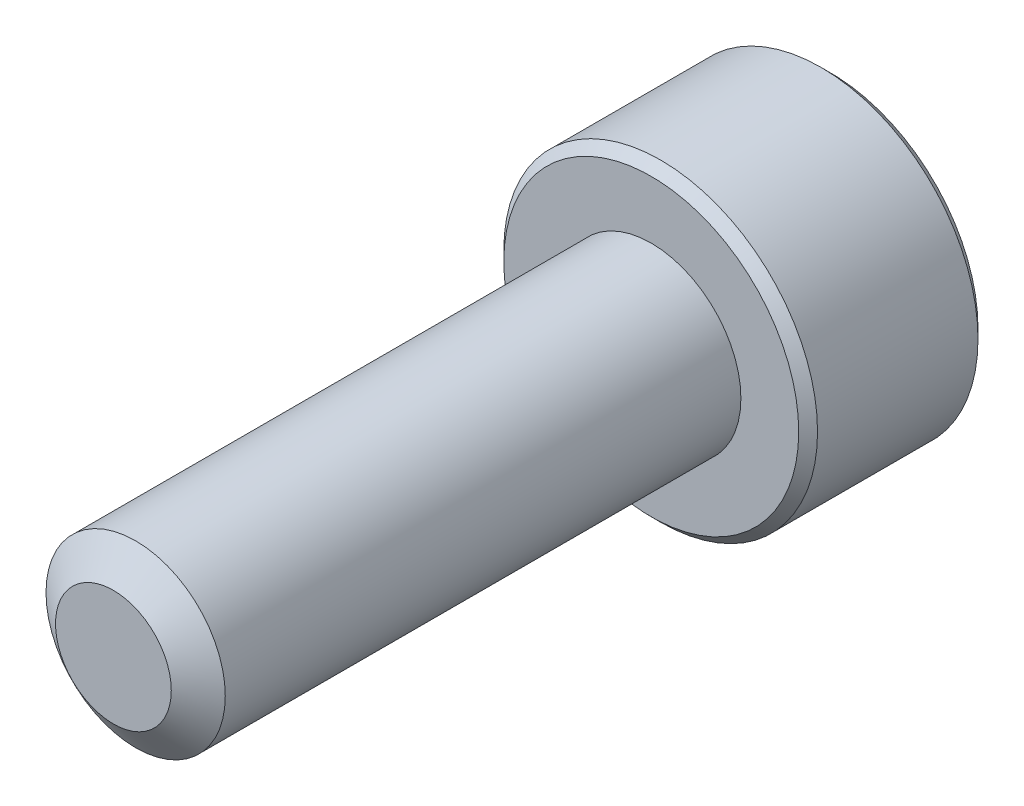
SolidWorks part; units mm, degrees
ref_plane "Front Plane" through (0, 0, 0) normal (0, 0, 1) x (1, 0, 0)
ref_plane "Top Plane" through (0, 0, 0) normal (0, 1, 0) x (1, 0, 0)
ref_plane "Right Plane" through (0, 0, 0) normal (1, 0, 0) x (0, 0, -1)
sketch "Sketch1" plane through (0, 0, 0) normal (0, 0, 1) x (1, 0, 0)
  circle A0 centre (0, 0) radius 2
  dimension "OD" = 4
extrude "Extrude1" add sketch "Sketch1" against normal blind 12
sketch "Sketch2" plane through (0, 0, 0) normal (0, 0, 1) x (1, 0, 0)
  circle A0 centre (0, 0) radius 2 construction
  circle A1 centre (0, 0) radius 2
curve "Helix/Spiral1" pitch 0.7 height 12.7 turns 18.1429 parameters "pitch"=0.7
sketch "Sketch3" plane through (0, 0, 0) normal (1, 0, 0) x (0, 0, -1)
  line L0 (-0.6125, 2) -> (-0.35, 1.5453)
  line L1 (-0.35, 1.5453) -> (-0.2625, 1.5453)
  line L2 (-0.2625, 1.5453) -> (0, 2)
  line L3 (-0.6125, 2) -> (0, 2)
  line L4 (-0.3063, 2) -> (-0.3063, 1.5453) construction
  line L5 (-0.4813, 1.7727) -> (-0.1313, 1.7727) construction
  line L6 (0, 2) -> (0, -2) construction
  line L7 (0, -2) -> (12, -2) construction
  point P11 (3.15, -2)
  dimension "D1" = 0.0875
  dimension "D2" = 0.35
  dimension "D3" = 60
  dimension "D4" = 3.15
sweep "Cut-Sweep1" [suppressed] cut profiles "Sketch3" path "Helix/Spiral1"
sketch "Sketch4" plane through (0, 0, 0) normal (1, 0, 0) x (0, 0, -1)
  line L0 (0.4962, 2) -> (0, 1.2913)
  line L1 (0, 1.2913) -> (0, 2)
  line L2 (0.4962, 2) -> (0, 2)
  line L3 (-0.6125, 2) -> (0, 2) construction
  line L4 (0, 0) -> (7.0209, 0) construction
  dimension "D1" = 55
  dimension "D2" = 0.254
revolve "Cut-Revolve1" cut sketch "Sketch4" angle 360 about L4
sketch "Sketch5" [suppressed] plane through (0, 0, 0) normal (1, 0, 0) x (0, 0, -1)
  line L0 (12, -0.9741) -> (12, 1.9864) construction
  line L1 (12, 2) -> (0.1203, 2)
  line L2 (12, 2) -> (12, 0)
  line L3 (12, 0) -> (0.0001, 0)
  line L4 (0.0001, 1.6698) -> (0.0001, 0)
  line L5 (0.1203, 2) -> (0.0001, 1.6698)
  line L6 (0, 0) -> (9.9695, 0) construction
  point P3 (0.0001, 2)
  point P10 (0.0001, 2)
  dimension "D1" = 0.3302
  dimension "Thread min" = 0.0001
  dimension "D3" = 20
revolve "partially thread" [suppressed] add sketch "Sketch5" angle 360 about L6
sketch "Sketch6" plane through (0, 0, -12) normal (0, 0, -1) x (-1, 0, 0)
  circle A0 centre (0, 0) radius 3.5
  dimension "head dia" = 7
extrude "Extrude2" add sketch "Sketch6" along normal blind 4
sketch "Sketch7" plane through (0, 0, -16) normal (0, 0, -1) x (-1, 0, 0)
  line L1 (0, 1.7321) -> (-1.5, 0.866)
  line L2 (-1.5, 0.866) -> (-1.5, -0.866)
  line L3 (-1.5, -0.866) -> (0, -1.7321)
  line L4 (0, -1.7321) -> (1.5, -0.866)
  line L5 (1.5, -0.866) -> (1.5, 0.866)
  line L6 (1.5, 0.866) -> (0, 1.7321)
  circle A0 centre (0, 0) radius 1.5 construction
  dimension "hex dia" = 3
extrude "Cut-Extrude1" cut sketch "Sketch7" against normal blind 2.25
sketch "Sketch8" plane through (0, 0, -16) normal (0, 0, -1) x (-1, 0, 0)
  circle A0 centre (0, 0) radius 1.7321
extrude "Cut-Extrude2" cut sketch "Sketch8" against normal through all draft 45
chamfer "Chamfer1" distance 0.21 angle 45 2 edges at (-3.5, 0, -16) (-3.5, 0, -12)
sketch "Sketch9" plane through (0, 0, 0) normal (1, 0, 0) x (0, 0, -1)
  line L0 (0, 2) -> (0, -2) construction
  line L1 (3.85, 2) -> (3.85, -2) construction
  dimension "D1" = 3.85
sketch "Sketch10" plane through (0, 0, 0) normal (1, 0, 0) x (0, 0, -1)
  line L0 (12, 2) -> (12, 0)
  line L1 (12, 2) -> (11.825, 2)
  line L2 (11.825, 2) -> (10.9966, 0)
  line L3 (12, 0) -> (10.9966, 0)
  line L4 (12, 3.29) -> (12, -3.29) construction
  dimension "D1" = 22.5
  dimension "D2" = 0.175
revolve "Revolve1" add sketch "Sketch10" angle 360 about L3
equation "\"D3@Helix/Spiral1\" = \"screw length@Extrude1\"+\"pitch@Helix/Spiral1\""
equation "\"D1@Sketch3\" = \"pitch@Helix/Spiral1\"*.125"
equation "\"D2@Sketch3\" = \"pitch@Helix/Spiral1\"*.5"
equation "\"D1@Cut-Extrude1\" = \"hex dia@Sketch7\"*.75"
equation "\"D1@Chamfer1\" = \"head dia@Sketch6\"*.03"
equation "\"D1@Sketch9\" = \"pitch@Helix/Spiral1\"*5.5"
equation "\"D2@Sketch10\" = \"pitch@Helix/Spiral1\"*.25"
equation "\"D4@Sketch3\" = \"pitch@Helix/Spiral1\"*4.50"
